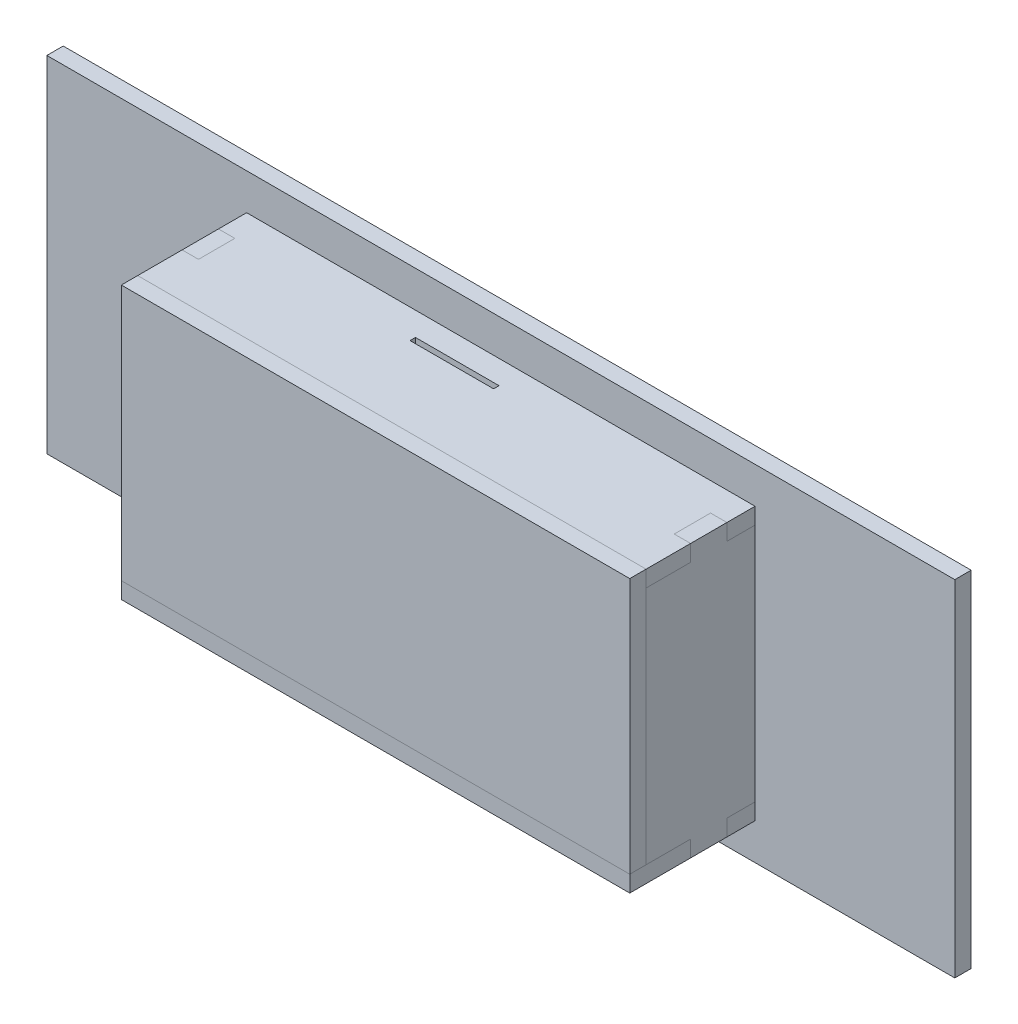
SolidWorks part; units mm, degrees
note: The reader was unsure of these and kept them because the rebuilt part matched: shared geometry of "Esquisse1<5>", "Esquisse1<6>", "Esquisse1<7>", "Esquisse1<8>", "Esquisse1<9>", "Esquisse1<10>".
other "boite_fond"
other "boite-droit"
other "boite-gauche"
other "boite-arriere"
other "boite-avant"
other "boite-couvercle" parameters "D1"=95.8861, "D2"=169.6, "D3"=280, "D4"=22.7836, "D5"=21.209, "D6"=46.0937, "D7"=30.481, "D8"=280, "D9"=280, "D10"=190
ref_plane "Plan de face" through (0, 0, 0) normal (0, 0, 1) x (1, 0, 0)
ref_plane "Plan de dessus" through (0, 0, 0) normal (0, 1, 0) x (1, 0, 0)
ref_plane "Plan de droite" through (0, 0, 0) normal (1, 0, 0) x (0, 0, -1)
sketch "Esquisse1" plane through (0, 0, 0) normal (0, 0, 1) x (1, 0, 0)
  line L0 (-140, 18.75) -> (-140, -18.75)
  line L1 (-140, 75) -> (140, 75)
  line L2 (-140, 75) -> (-140, -75)
  line L3 (-140, -75) -> (140, -75)
  line L4 (140, 75) -> (140, -75)
  line L5 (140, 56.25) -> (140, 75)
  line L6 (0, 75) -> (0, -75) construction
  line L7 (-140, 0) -> (140, 0) construction
  line L8 (-131, 66) -> (-131, -66)
  line L9 (-131, -66) -> (131, -66)
  line L10 (131, 66) -> (131, -66)
  line L11 (-131, 66) -> (131, 66)
  line L12 (17.5, 75) -> (-17.5, 75)
  line L13 (-17.5, 75) -> (-17.5, 66)
  line L14 (-17.5, 66) -> (-52.5, 66)
  line L15 (-52.5, 66) -> (-52.5, 75)
  line L16 (-52.5, 75) -> (-87.5, 75)
  line L17 (-87.5, 75) -> (-87.5, 66)
  line L18 (-87.5, 66) -> (-122.5, 66)
  line L19 (-122.5, 66) -> (-122.5, 75)
  line L20 (-122.5, 75) -> (-140, 75)
  line L21 (17.5, 75) -> (17.5, 66)
  line L22 (17.5, 66) -> (52.5, 66)
  line L23 (52.5, 66) -> (52.5, 75)
  line L24 (52.5, 75) -> (87.5, 75)
  line L25 (87.5, 75) -> (87.5, 66)
  line L26 (87.5, 66) -> (122.5, 66)
  line L27 (122.5, 66) -> (122.5, 75)
  line L28 (122.5, 75) -> (140, 75)
  line L29 (-131, -66) -> (131, -66)
  line L30 (-140, -75) -> (140, -75)
  line L49 (-140, 18.75) -> (-131, 18.75)
  line L50 (-131, 18.75) -> (-131, 56.25)
  line L51 (-131, 56.25) -> (-140, 56.25)
  line L52 (-140, 56.25) -> (-140, 75)
  line L57 (131, 66) -> (131, -66)
  line L58 (140, 75) -> (140, -75)
  line L59 (131, 56.25) -> (140, 56.25)
  line L60 (131, 18.75) -> (131, 56.25)
  line L61 (140, 18.75) -> (131, 18.75)
  line L62 (140, 18.75) -> (140, -18.75)
  line L64 (140, -18.75) -> (131, -18.75)
  line L65 (131, -18.75) -> (131, -56.25)
  line L66 (131, -56.25) -> (140, -56.25)
  line L67 (-140, -56.25) -> (-140, -75)
  line L68 (-131, -56.25) -> (-140, -56.25)
  line L69 (-131, -18.75) -> (-131, -56.25)
  line L70 (-140, -18.75) -> (-131, -18.75)
  line L71 (122.5, -75) -> (140, -75)
  line L72 (122.5, -66) -> (122.5, -75)
  line L73 (87.5, -66) -> (122.5, -66)
  line L74 (87.5, -75) -> (87.5, -66)
  line L75 (52.5, -75) -> (87.5, -75)
  line L76 (52.5, -66) -> (52.5, -75)
  line L77 (17.5, -66) -> (52.5, -66)
  line L78 (17.5, -75) -> (17.5, -66)
  line L79 (-122.5, -75) -> (-140, -75)
  line L80 (-122.5, -66) -> (-122.5, -75)
  line L81 (-87.5, -66) -> (-122.5, -66)
  line L82 (-87.5, -75) -> (-87.5, -66)
  line L83 (-52.5, -75) -> (-87.5, -75)
  line L84 (-52.5, -66) -> (-52.5, -75)
  line L85 (-17.5, -66) -> (-52.5, -66)
  line L86 (-17.5, -75) -> (-17.5, -66)
  line L87 (17.5, -75) -> (-17.5, -75)
  line L88 (140, -56.25) -> (140, -75)
  line L89 (-131, 66) -> (-131, 75)
  line L90 (-131, 66) -> (-140, 66)
  line L91 (131, 66) -> (131, 75)
  line L92 (131, 66) -> (140, 66)
  line L93 (-131, -66) -> (-140, -66)
  line L94 (-131, -66) -> (-131, -75)
  line L95 (131, -66) -> (140, -66)
  line L96 (131, -66) -> (131, -75)
  line L98 (250, -95) -> (-250, -95)
  line L99 (250, -95) -> (250, 95)
  line L100 (250, 95) -> (-250, 95)
  line L101 (-250, -95) -> (-250, 95)
  point P1 (0, 0)
  point P74 (0, -95)
  dimension "D1" = 280
  dimension "D2" = 150
  dimension "D4" = 17.5
  dimension "D5" = 35
  dimension "D6" = 18.75
  dimension "D7" = 37.5
  dimension "D8" = 20
  dimension "D9" = 20
  dimension "D10" = 500
  dimension "D3" = 9
extrude "Boss.-Extru.1" add sketch "Esquisse1" along normal blind 9 contours L11 L8 L9 L29 L10 L57 | L51 L8 L11 L19 L1 L2 | L1 L17 L11 L15 | L21 L1 L13 L11 | L25 L1 L23 L11 | L10 L59 L4 L1 L27 L11 | L64 L58 L61 L10 | L29 L76 L30 L74 | L86 L3 L78 L9 | L29 L72 L30 L58 L66 L10 | L84 L9 L82 L3 | L80 L9 L8 L68 L2 L3 | L0 L70 L8 L49 | L9 L94 L79 L80 | L94 L93 L67 L3 | L90 L89 L1 L2 | L89 L11 L19 L20 | L11 L91 L1 L27 | L91 L92 L4 L28 | L96 L29 L72 L30 | L95 L96 L71 L88 | L101 L98 L99 L100 L1 L20 L28 L4 L58 L88 L71 L30 L3 L79 L67 L2 L0 L52
extrude "Boss.-Extru.2" add sketch "Esquisse1<5>" along normal blind 60 from surface at 9 separate body contours L90 L89 L1 L2 | L8 L90 L52 L51 | L8 L51 L2 L49 | L0 L70 L8 L49 | L70 L2 L68 L8 | L93 L8 L68 L2 | L94 L93 L67 L3 starting at face at (105, 70.5, 9)
sketch "Esquisse1<5>" plane through (0, 0, 0) normal (0, 0, 1) x (1, 0, 0) same geometry as "Esquisse1"
extrude "Boss.-Extru.3" add sketch "Esquisse1<6>" along normal up to surface (9 mm away) contours L8 L51 L2 L49 | L70 L2 L68 L8 up to face at (-135.5, 0, 9)
sketch "Esquisse1<6>" plane through (0, 0, 0) normal (0, 0, 1) x (1, 0, 0) same geometry as "Esquisse1"
sketch "Esquisse2" plane through (-140, 0, 0) normal (-1, 0, 0) x (0, 0, 1)
  line L0 (9, 66) -> (60, 66)
  line L1 (0, 75) -> (69, 75)
  line L2 (0, 75) -> (0, -75)
  line L3 (0, -75) -> (69, -75)
  line L4 (69, 75) -> (69, -75)
  line L5 (60, 66) -> (60, -66)
  line L6 (9, -66) -> (60, -66)
  line L7 (9, 66) -> (9, -66)
  line L8 (24.5, 75) -> (24.5, 66)
  line L9 (24.5, 66) -> (0, 66)
  line L10 (44.5, 66) -> (69, 66)
  line L11 (44.5, 75) -> (44.5, 66)
  line L12 (44.5, -75) -> (44.5, -66)
  line L13 (34.5, 66) -> (34.5, -66) construction
  line L14 (9, 0) -> (60, 0) construction
  line L15 (44.5, -66) -> (69, -66)
  line L16 (24.5, -66) -> (0, -66)
  line L17 (24.5, -75) -> (24.5, -66)
  line L18 (9, 56.25) -> (9, 18.75) construction
  line L19 (69, 75) -> (9, 75) construction
  point P12 (0, 0)
  point P13 (0, 0)
  point P16 (0, 0)
  line M5 (9, -56.25) -> (9, -75)
  line M6 (9, -75) -> (69, -75)
  line M7 (69, -75) -> (69, 75)
  line M8 (69, 75) -> (9, 75)
  line M9 (9, 75) -> (9, 56.25)
  dimension "D2" = 10
  dimension "D1" = 9
extrude "Enlèv. mat.-Extru.1" cut sketch "Esquisse2" against normal through all contours L8 L1 L0 M9 | L9 L1 L2 M9 | L11 L0 L10 L4 M8 | L15 L6 L12 L3 M7 | L17 L6 M6 M5 | L16 L2 L3 M5
mirror "Symétrie1" about plane through (0, 0, 0) normal (1, 0, 0) of bodies 105
extrude "Boss.-Extru.4" add sketch "Esquisse1<7>" along normal up to surface (60 mm away) from surface at 9 separate body contours L84 L9 L82 L3 | L30 L86 L29 L84 | L86 L3 L78 L9 | L78 L30 L76 L29 | L29 L76 L30 L74 | L74 L30 L72 L29 | L96 L29 L72 L30 | L95 L96 L71 L88 | L30 L82 L29 L80 | L9 L94 L79 L80 | L94 L93 L67 L3 up to face at (-135.5, 0, 69) starting at face at (105, 70.5, 9)
sketch "Esquisse1<7>" plane through (0, 0, 0) normal (0, 0, 1) x (1, 0, 0) same geometry as "Esquisse1"
extrude "Boss.-Extru.5" add sketch "Esquisse1<8>" along normal up to surface (9 mm away) contours L30 L82 L29 L80 | L30 L86 L29 L84 | L78 L30 L76 L29 | L74 L30 L72 L29 up to face at (0, -70.5, 9)
sketch "Esquisse1<8>" plane through (0, 0, 0) normal (0, 0, 1) x (1, 0, 0) same geometry as "Esquisse1"
sketch "Esquisse3" plane through (0, -75, 0) normal (0, -1, 0) x (1, 0, 0)
  line L0 (0, 69) -> (0, 0) construction
  line L1 (-131, 44.5) -> (-140, 44.5)
  line L2 (-131, 44.5) -> (-131, 24.5)
  line L3 (-131, 24.5) -> (-140, 24.5)
  line L4 (-140, 44.5) -> (-140, 24.5)
  line L5 (-140, 69) -> (140, 69) construction
  line L6 (131, 24.5) -> (140, 24.5)
  line L7 (140, 44.5) -> (140, 24.5)
  line L8 (131, 44.5) -> (140, 44.5)
  line L9 (131, 44.5) -> (131, 24.5)
extrude "Enlèv. mat.-Extru.2" cut sketch "Esquisse3" against normal through all
mirror "Symétrie2" about plane through (0, 0, 0) normal (0, 1, 0) of bodies 109
extrude "Boss.-Extru.6" add sketch "Esquisse1<9>" along normal blind 9 from surface at 69 contours L95 L96 L71 L88 | L96 L29 L72 L30 | L74 L30 L72 L29 | L29 L76 L30 L74 | L78 L30 L76 L29 | L86 L3 L78 L9 | L30 L86 L29 L84 | L84 L9 L82 L3 | L30 L82 L29 L80 | L9 L94 L79 L80 | L94 L93 L67 L3 starting at face at (0, -70.5, 69)
sketch "Esquisse1<9>" plane through (0, 0, 0) normal (0, 0, 1) x (1, 0, 0) same geometry as "Esquisse1"
extrude "Boss.-Extru.7" add sketch "Esquisse1<10>" along normal up to surface (9 mm away) from surface at 69 separate body contours L11 L8 L9 L29 L10 L57 | L10 L95 L58 L66 | L57 L66 L4 L64 | L64 L58 L61 L10 | L61 L4 L59 L57 | L91 L92 L4 L28 | L11 L91 L1 L27 | L11 L27 L1 L25 | L25 L1 L23 L11 | L11 L23 L1 L21 | L21 L1 L13 L11 | L15 L11 L13 L1 | L1 L17 L11 L15 | L19 L11 L17 L1 | L90 L89 L1 L2 | L8 L90 L52 L51 | L89 L11 L19 L20 | L8 L51 L2 L49 | L0 L70 L8 L49 | L70 L2 L68 L8 | L93 L8 L68 L2 | L92 L10 L59 L58
sketch "Esquisse1<10>" plane through (0, 0, 0) normal (0, 0, 1) x (1, 0, 0) same geometry as "Esquisse1"
sketch "Esquisse4" plane through (0, 75, 0) normal (0, 1, 0) x (1, 0, 0)
  line L0 (-131, -44.5) -> (-131, -24.5) construction
  line L1 (-34, -25) -> (12, -25)
  line L2 (-34, -25) -> (-34, -22)
  line L3 (-34, -22) -> (12, -22)
  line L4 (12, -25) -> (12, -22)
  line L5 (17.5, -9) -> (-17.5, -9) construction
  dimension "D1" = 3
  dimension "D2" = 46
  dimension "D3" = 97
  dimension "D4" = 13
extrude "Enlèv. mat.-Extru.3" cut sketch "Esquisse4" against normal blind 10
other "Enregistrer les corps1"
equation "\"D4@Esquisse1\" = \"largeur\" / 16"
equation "\"D5@Esquisse1\" = \"largeur\" / 8"
equation "\"D6@Esquisse1\" = \"profondeur\" / 8"
equation "\"D7@Esquisse1\" = \"profondeur\" / 4"
equation "\"largeur\"= 280"
equation "\"hauteur\"= 60"
equation "\"profondeur\"= 150"
equation "\"D1@Esquisse1\"= \"largeur\""
equation "\"D2@Esquisse1\"= \"profondeur\""
equation "\"D1@Boss.-Extru.2\"=\"hauteur\""
equation "\"D1@Esquisse2\" = \"tailleBois\""
equation "\"tailleBois\"= 9"
equation "\"D2@Esquisse2\"=\"hauteur\"/6"
equation "\"D1@Boss.-Extru.6\"=\"tailleBois\""
